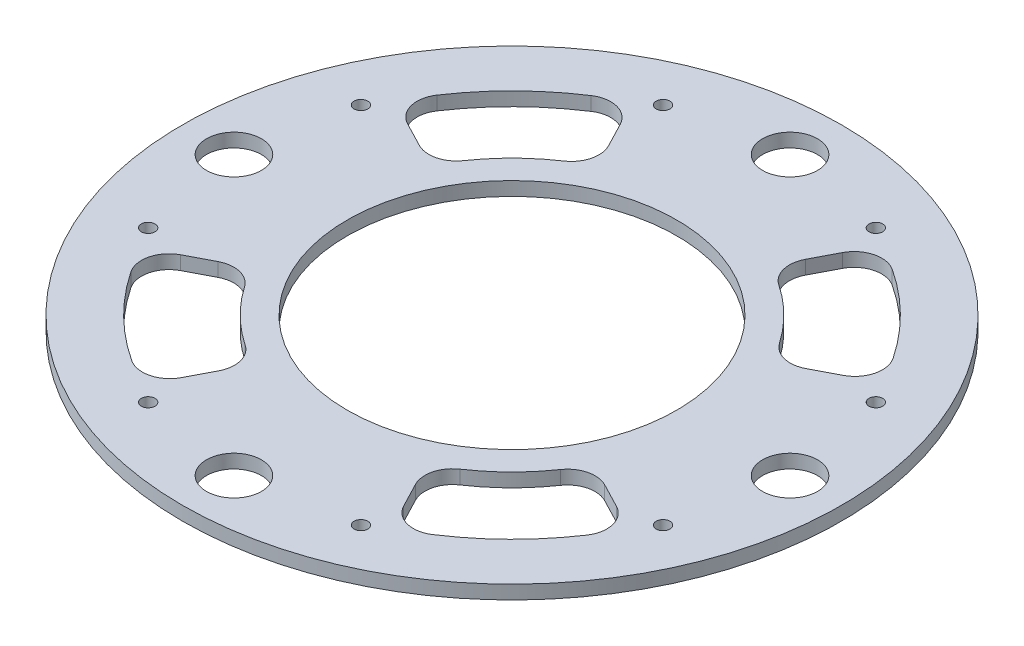
SolidWorks part; units mm, degrees
material "Acrylic (Medium-high impact)"
ref_plane "Front Plane" through (0, 0, 0) normal (0, 0, 1) x (1, 0, 0)
ref_plane "Top Plane" through (0, 0, 0) normal (0, 1, 0) x (1, 0, 0)
ref_plane "Right Plane" through (0, 0, 0) normal (1, 0, 0) x (0, 0, -1)
sketch "Sketch1" plane through (0, 0, 0) normal (0, 1, 0) x (1, 0, 0)
  circle A0 centre (0, 0) radius 76.2
  dimension "D1" = 152.4
extrude "Boss-Extrude1" add sketch "Sketch1" along normal blind 3.175
sketch "Sketch2" plane through (0, 3.175, 0) normal (0, 1, 0) x (1, 0, 0)
  circle A0 centre (0, 0) radius 35
  dimension "D1" = 70
extrude "Cut-Extrude1" cut sketch "Sketch2" against normal blind 6.35
sketch "Sketch3" plane through (0, 3.175, 0) normal (0, 1, 0) x (1, 0, 0)
  line L0 (-76.2, 0) -> (76.2, 0) construction
  line L1 (-51.5875, 51.5875) -> (51.5875, 51.5875) construction
  line L2 (-51.5875, 51.5875) -> (-51.5875, -51.5875) construction
  line L3 (-51.5875, -51.5875) -> (51.5875, -51.5875) construction
  line L4 (51.5875, 51.5875) -> (51.5875, -51.5875) construction
  circle A0 centre (0, 0) radius 76.2 construction
  circle A1 centre (-64.2875, 0) radius 6.35
  circle A2 centre (64.2875, 0) radius 6.35
  dimension "D1" = 12.7
  dimension "D2" = 12.7
  dimension "D3" = 12.7
  dimension "D4" = 12.7
extrude "Cut-Extrude2" cut sketch "Sketch3" against normal blind 10
sketch "Sketch4" plane through (0, 3.175, 0) normal (0, 1, 0) x (1, 0, 0)
  line L1 (50, -50) -> (-50, -50) construction
  line L2 (50, -50) -> (50, 50) construction
  line L3 (50, 50) -> (-50, 50) construction
  line L4 (-50, -50) -> (-50, 50) construction
  line L5 (50, -50) -> (-50, 50) construction
  line L6 (50, 50) -> (-50, -50) construction
  point P0 (0, 0)
  dimension "D1" = 100
  dimension "D2" = 100
sketch "Sketch5" plane through (0, 3.175, 0) normal (0, 1, 0) x (1, 0, 0)
  line L0 (-50, 24.6) -> (-59.525, 24.6) construction
  line L1 (-50, -50) -> (-50, 50) construction
  line L2 (-50, -24.6) -> (-59.525, -24.6) construction
  line L3 (50, 50) -> (-50, 50) construction
  line L4 (50, -50) -> (-50, -50) construction
  line L5 (-50, 50) -> (50, -50) construction
  line L6 (-50, -50) -> (50, 50) construction
  line L7 (24.6, 50) -> (24.6, 59.525) construction
  line L8 (-50, 50) -> (50, 50) construction
  line L9 (-50, 50) -> (-50, -50) construction
  line L10 (-50, -50) -> (50, -50) construction
  line L11 (50, 50) -> (50, -50) construction
  line L12 (-24.6, 50) -> (-24.6, 59.525) construction
  line L13 (50, 24.6) -> (59.525, 24.6) construction
  line L14 (-24.6, -50) -> (-24.6, -59.525) construction
  line L15 (24.6, -50) -> (24.6, -59.525) construction
  line L16 (50, -24.6) -> (59.525, -24.6) construction
  dimension "D1" = 25.4
  dimension "D2" = 25.4
  dimension "D3" = 9.525
  dimension "D4" = 9.525
sketch "Sketch7" plane through (0, 3.175, 0) normal (0, 1, 0) x (1, 0, 0)
  line L0 (0, 0) -> (0, 76.2) construction
  line L1 (0, 0) -> (53.8815, 53.8815) construction
  line L2 (0, 59.5249) -> (-24.5999, 59.5249) construction
  line L3 (0, 0) -> (76.2, 0) construction
  line L4 (0, -59.5249) -> (-24.5999, -59.5249) construction
  circle A0 centre (0, 0) radius 76.2 construction
  circle A1 centre (-24.5999, 59.5249) radius 1.5875
  circle A2 centre (24.5999, 59.5249) radius 1.5875
  circle A3 centre (24.5999, -59.5249) radius 1.5875
  circle A4 centre (-24.5999, -59.5249) radius 1.5875
  circle A5 centre (-59.5249, 24.5999) radius 1.5875
  circle A6 centre (-59.5249, -24.5999) radius 1.5875
  circle A7 centre (59.5249, 24.5999) radius 1.5875
  circle A8 centre (59.5249, -24.5999) radius 1.5875
  dimension "D1" = 45
  dimension "D2" = 59.5249
  dimension "D3" = 24.5999
extrude "Cut-Extrude4" cut sketch "Sketch7" against normal blind 10
sketch "Sketch8" plane through (0, 3.175, 0) normal (0, 1, 0) x (1, 0, 0)
  line L0 (0, 76.2) -> (0, -76.2) construction
  line L1 (0, 0) -> (53.8815, 53.8815) construction
  circle A0 centre (0, 0) radius 76.2 construction
  circle A1 centre (-64.2875, 0) radius 6.35
  circle A2 centre (64.2875, 0) radius 6.35
  circle A3 centre (0, -64.2875) radius 6.35
  circle A4 centre (0, 64.2875) radius 6.35
extrude "Cut-Extrude5" cut sketch "Sketch8" against normal blind 10
sketch "Sketch9" plane through (0, 3.175, 0) normal (0, 1, 0) x (1, 0, 0)
  circle A0 centre (0, 0) radius 38.1
  dimension "D1" = 76.2
extrude "Cut-Extrude6" cut sketch "Sketch9" against normal blind 10
sketch "Sketch10" plane through (0, 3.175, 0) normal (0, 1, 0) x (1, 0, 0)
  line L0 (0, 0) -> (-76.2, 0) construction
  line L1 (0, 0) -> (0, 76.2) construction
  line L2 (0, 0) -> (-53.8815, 53.8815) construction
  line L3 (-22.7447, 45.0673) -> (-25.6934, 50.7318)
  line L4 (-44.7067, 23.2729) -> (-50.3788, 26.2255)
  line L5 (44.7067, 23.2729) -> (50.3788, 26.2255)
  line L6 (22.7447, 45.0673) -> (25.6934, 50.7318)
  line L7 (22.7447, -45.0673) -> (25.6934, -50.7318)
  line L8 (44.7067, -23.2729) -> (50.3788, -26.2255)
  line L9 (-44.7067, -23.2729) -> (-50.3788, -26.2255)
  line L10 (-22.7447, -45.0673) -> (-25.6934, -50.7318)
  circle A0 centre (0, 0) radius 76.2 construction
  arc A1 (-24.83, 36.8683) -> (-36.5528, 25.2922) centre (0, 0) ccw
  arc A2 (-34.8066, 53.1108) -> (-52.7185, 35.3978) centre (0, 0) ccw
  circle A3 centre (0, 0) radius 38.1 construction
  arc A4 (-52.7185, 35.3978) -> (-50.3788, 26.2255) centre (-47.4467, 31.8581) ccw
  arc A5 (-44.7067, 23.2729) -> (-36.5528, 25.2922) centre (-41.7746, 28.9054) ccw
  arc A6 (-24.83, 36.8683) -> (-22.7447, 45.0673) centre (-28.3772, 42.1352) ccw
  arc A7 (-25.6934, 50.7318) -> (-34.8066, 53.1108) centre (-31.3259, 47.7997) ccw
  arc A8 (25.6934, 50.7318) -> (34.8066, 53.1108) centre (31.3259, 47.7997) cw
  arc A9 (24.83, 36.8683) -> (22.7447, 45.0673) centre (28.3772, 42.1352) cw
  arc A10 (44.7067, 23.2729) -> (36.5528, 25.2922) centre (41.7746, 28.9054) cw
  arc A11 (52.7185, 35.3978) -> (50.3788, 26.2255) centre (47.4467, 31.8581) cw
  arc A12 (34.8066, 53.1108) -> (52.7185, 35.3978) centre (0, 0) cw
  arc A13 (24.83, 36.8683) -> (36.5528, 25.2922) centre (0, 0) cw
  arc A14 (24.83, -36.8683) -> (36.5528, -25.2922) centre (0, 0) ccw
  arc A15 (34.8066, -53.1108) -> (52.7185, -35.3978) centre (0, 0) ccw
  arc A16 (52.7185, -35.3978) -> (50.3788, -26.2255) centre (47.4467, -31.8581) ccw
  arc A17 (44.7067, -23.2729) -> (36.5528, -25.2922) centre (41.7746, -28.9054) ccw
  arc A18 (24.83, -36.8683) -> (22.7447, -45.0673) centre (28.3772, -42.1352) ccw
  arc A19 (25.6934, -50.7318) -> (34.8066, -53.1108) centre (31.3259, -47.7997) ccw
  arc A20 (-25.6934, -50.7318) -> (-34.8066, -53.1108) centre (-31.3259, -47.7997) cw
  arc A21 (-24.83, -36.8683) -> (-22.7447, -45.0673) centre (-28.3772, -42.1352) cw
  arc A22 (-44.7067, -23.2729) -> (-36.5528, -25.2922) centre (-41.7746, -28.9054) cw
  arc A23 (-52.7185, -35.3978) -> (-50.3788, -26.2255) centre (-47.4467, -31.8581) cw
  arc A24 (-34.8066, -53.1108) -> (-52.7185, -35.3978) centre (0, 0) cw
  arc A25 (-24.83, -36.8683) -> (-36.5528, -25.2922) centre (0, 0) cw
  circle A26 centre (0, 0) radius 76.2
  dimension "D4" = 6.35
  dimension "D5" = 152.4
  dimension "D6" = 6.35
  dimension "D7" = 12.7
  dimension "D1" = 45
  dimension "D2" = 27.5
  dimension "D3" = 27.5
extrude "Cut-Extrude10" cut sketch "Sketch10" against normal blind 10 contours L3 A7 A2 A4 L4 A5 A1 A6 | A9 A13 A10 L5 A11 A12 A8 L6 | L7 A19 A15 A16 L8 A17 A14 A18 | A21 A25 A22 L9 A23 A24 A20 L10 region at (-37.7369, 3.175, -38.1823) region at (37.7369, 3.175, -38.1823) region at (37.7369, 3.175, 38.1823) region at (-37.7369, 3.175, 38.1823)
sketch "Sketch11" plane through (0, 3.175, 0) normal (0, 1, 0) x (1, 0, 0)
  line L0 (-25.6934, 50.7318) -> (-22.7447, 45.0673)
  line L1 (-44.7067, 23.2729) -> (-50.3788, 26.2255)
  line L4 (44.7067, 23.2729) -> (50.3788, 26.2255)
  line L5 (25.6934, 50.7318) -> (22.7447, 45.0673)
  line L6 (25.6934, -50.7318) -> (22.7447, -45.0673)
  line L7 (44.7067, -23.2729) -> (50.3788, -26.2255)
  line L8 (-44.7067, -23.2729) -> (-50.3788, -26.2255)
  line L9 (-25.6934, -50.7318) -> (-22.7447, -45.0673)
  circle A0 centre (0, 0) radius 38.1
  circle A1 centre (0, 0) radius 76.2
  arc A2 (-24.83, 36.8683) -> (-36.5528, 25.2922) centre (0, 0) ccw
  arc A3 (34.8066, 53.1108) -> (52.7185, 35.3978) centre (0, 0) cw
  circle A4 centre (0, 64.2875) radius 6.5947
  circle A5 centre (-64.2875, 0) radius 6.35
  circle A6 centre (-59.5249, 24.5999) radius 1.5875
  circle A7 centre (-24.5999, 59.5249) radius 1.5875
  arc A8 (-50.3788, 26.2255) -> (-52.7185, 35.3978) centre (-47.4467, 31.8581) cw
  arc A9 (-44.7067, 23.2729) -> (-36.5528, 25.2922) centre (-41.7746, 28.9054) ccw
  arc A10 (-22.7447, 45.0673) -> (-24.83, 36.8683) centre (-28.3772, 42.1352) cw
  arc A11 (-25.6934, 50.7318) -> (-34.8066, 53.1108) centre (-31.3259, 47.7997) ccw
  arc A12 (-34.8066, 53.1108) -> (-52.7185, 35.3978) centre (0, 0) ccw
  arc A13 (25.6934, 50.7318) -> (34.8066, 53.1108) centre (31.3259, 47.7997) cw
  arc A14 (22.7447, 45.0673) -> (24.83, 36.8683) centre (28.3772, 42.1352) ccw
  arc A15 (44.7067, 23.2729) -> (36.5528, 25.2922) centre (41.7746, 28.9054) cw
  arc A16 (50.3788, 26.2255) -> (52.7185, 35.3978) centre (47.4467, 31.8581) ccw
  circle A17 centre (24.5999, 59.5249) radius 1.5875
  circle A18 centre (59.5249, 24.5999) radius 1.5875
  circle A19 centre (64.2875, 0) radius 6.35
  arc A20 (24.83, 36.8683) -> (36.5528, 25.2922) centre (0, 0) cw
  arc A21 (24.83, -36.8683) -> (36.5528, -25.2922) centre (0, 0) ccw
  circle A22 centre (59.5249, -24.5999) radius 1.5875
  circle A23 centre (24.5999, -59.5249) radius 1.5875
  arc A24 (50.3788, -26.2255) -> (52.7185, -35.3978) centre (47.4467, -31.8581) cw
  arc A25 (44.7067, -23.2729) -> (36.5528, -25.2922) centre (41.7746, -28.9054) ccw
  arc A26 (22.7447, -45.0673) -> (24.83, -36.8683) centre (28.3772, -42.1352) cw
  arc A27 (25.6934, -50.7318) -> (34.8066, -53.1108) centre (31.3259, -47.7997) ccw
  arc A28 (34.8066, -53.1108) -> (52.7185, -35.3978) centre (0, 0) ccw
  arc A29 (-34.8066, -53.1108) -> (-52.7185, -35.3978) centre (0, 0) cw
  arc A30 (-25.6934, -50.7318) -> (-34.8066, -53.1108) centre (-31.3259, -47.7997) cw
  arc A31 (-22.7447, -45.0673) -> (-24.83, -36.8683) centre (-28.3772, -42.1352) ccw
  arc A32 (-44.7067, -23.2729) -> (-36.5528, -25.2922) centre (-41.7746, -28.9054) cw
  arc A33 (-50.3788, -26.2255) -> (-52.7185, -35.3978) centre (-47.4467, -31.8581) ccw
  circle A34 centre (-24.5999, -59.5249) radius 1.5875
  circle A35 centre (-59.5249, -24.5999) radius 1.5875
  arc A36 (-24.83, -36.8683) -> (-36.5528, -25.2922) centre (0, 0) cw
  circle A37 centre (0, -64.2875) radius 6.35
